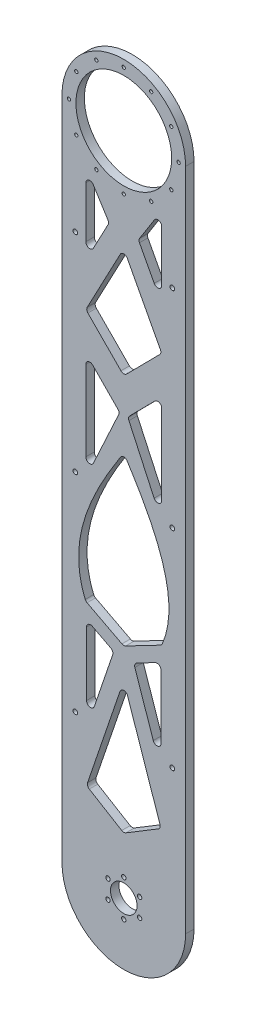
SolidWorks part; units mm, degrees
material "1060 Alloy"
ref_plane "Front Plane" through (0, 0, 0) normal (0, 0, 1) x (1, 0, 0)
ref_plane "Top Plane" through (0, 0, 0) normal (0, 1, 0) x (1, 0, 0)
ref_plane "Right Plane" through (0, 0, 0) normal (1, 0, 0) x (0, 0, -1)
sketch "Sketch2" plane through (0, 0, 0) normal (0, 0, 1) x (1, 0, 0)
  line L0 (0, 0) -> (0, 500) construction
  line L1 (-46.5, 0) -> (-46.5, 500)
  line L2 (46.5, 0) -> (46.5, 500)
  arc A0 (-46.5, 0) -> (46.5, 0) centre (0, 0) ccw
  arc A1 (46.5, 500) -> (-46.5, 500) centre (0, 500) ccw
  circle A2 centre (0, 500) radius 37.25 construction
  circle A3 centre (0, 0) radius 10
  circle A4 centre (0, 13.75) radius 1.65
  circle A5 centre (0, 0) radius 13.75 construction
  circle A6 centre (11.9078, 6.875) radius 1.65
  circle A7 centre (11.9078, -6.875) radius 1.65
  circle A8 centre (0, -13.75) radius 1.65
  circle A9 centre (-11.9078, -6.875) radius 1.65
  circle A10 centre (-11.9078, 6.875) radius 1.65
  point P3 (0, 250)
  point P27 (0, 0)
  dimension "D2" = 74.5
  dimension "D4" = 20
  dimension "D5" = 3.3
  dimension "D6" = 27.5
  dimension "D3" = 46.5
  dimension "D1" = 500
  dimension "D7" = 6
extrude "Boss-Extrude1" add sketch "Sketch2" along normal blind 6.35
sketch "Sketch4" plane through (0, 0, 6.35) normal (0, 0, 1) x (1, 0, 0)
  line L0 (0, 500) -> (0, 999.1647) construction
  line L29 (46.5, 500) -> (-46.5, 500) construction
  line L31 (28.0053, 59.376) -> (0, 42.4117)
  line L32 (0, 141.6934) -> (28.0053, 59.376)
  line L33 (-28.0053, 59.376) -> (0, 141.6934)
  line L34 (0, 42.4117) -> (-28.0053, 59.376)
  line L35 (-7.5, 156.9059) -> (-28.0053, 96.6336)
  line L36 (-28.0053, 167.5829) -> (-7.5, 156.9059)
  line L37 (-28.0053, 96.6336) -> (-28.0053, 167.5829)
  line L38 (28.0053, 167.5829) -> (7.5, 156.9059)
  line L39 (28.0053, 96.6336) -> (28.0053, 167.5829)
  line L40 (7.5, 156.9059) -> (28.0053, 96.6336)
  line L41 (0, 164.2751) -> (28.5505, 179.1412)
  line L42 (0, 164.2751) -> (-28.5505, 179.1412)
  line L43 (28.5505, 259.5868) -> (3, 314.9383)
  line L44 (28.5505, 340.7931) -> (28.5505, 259.5868)
  line L45 (3, 314.9383) -> (28.5505, 340.7931)
  line L46 (-3, 314.9383) -> (-28.5505, 340.7931)
  line L47 (-28.5505, 259.5868) -> (-3, 314.9383)
  line L48 (-28.5505, 340.7931) -> (-28.5505, 259.5868)
  line L49 (0, 423.1428) -> (-28.5505, 369.2462)
  line L50 (-28.5505, 369.2462) -> (0, 340.3557)
  line L51 (0, 340.3557) -> (28.5505, 369.2462)
  line L52 (0, 423.1428) -> (28.5505, 369.2462)
  line L53 (-28.5505, 462.0952) -> (-28.5505, 401.2902)
  line L54 (-11, 434.4215) -> (-28.5505, 462.0952)
  line L55 (-28.5505, 401.2902) -> (-11, 434.4215)
  line L56 (28.5505, 401.2902) -> (11, 434.4215)
  line L57 (28.5505, 462.0952) -> (28.5505, 401.2902)
  line L58 (11, 434.4215) -> (28.5505, 462.0952)
  arc A0 (46.5, 500) -> (-46.5, 500) centre (0, 500) ccw construction
  arc A1 (46.5, 500) -> (-46.5, 500) centre (0, 500) ccw construction
  spline S2 degree 3 poles (28.5505, 179.1412) (45.3203, 216.9857) (19.4301, 259.7903) (0, 290.0258) knots 0 0 0 0 1 1 1 1
  spline S3 degree 3 poles (-28.5505, 179.1412) (-45.3203, 216.9857) (-19.4301, 259.7903) (0, 290.0258) knots 0 0 0 0 1 1 1 1
extrude "Cut-Extrude1" cut sketch "Sketch4" against normal blind 10
fillet "Fillet3" radius 3 30 edges at (-11, 434.4215, 3.175) (-28.5505, 401.2902, 3.175) (28.5505, 401.2902, 3.175) (11, 434.4215, 3.175) (28.5505, 462.0952, 3.175) (-28.5505, 462.0952, 3.175) (0, 423.1428, 3.175) (-28.5505, 369.2462, 3.175) (28.5505, 369.2462, 3.175) (0, 340.3557, 3.175) (28.5505, 340.7931, 3.175) (-28.5505, 340.7931, 3.175) (-3, 314.9383, 3.175) (3, 314.9383, 3.175) (28.5505, 259.5868, 3.175) (-28.5505, 259.5868, 3.175) (28.5505, 179.1412, 3.175) (0, 290.0258, 3.175) (-28.5505, 179.1412, 3.175) (0, 164.2751, 3.175) (-28.0053, 96.6336, 3.175) (28.0053, 96.6336, 3.175) (7.5, 156.9059, 3.175) (-28.0053, 167.5829, 3.175) (28.0053, 167.5829, 3.175) (0, 141.6934, 3.175) (28.0053, 59.376, 3.175) (-28.0053, 59.376, 3.175) (0, 42.4117, 3.175) (-7.5, 156.9059, 3.175)
sketch "Sketch5" plane through (0, 0, 6.35) normal (0, 0, 1) x (1, 0, 0)
  line L0 (0, -46.5) -> (108.8395, -46.5) construction
  line L1 (46.5, 100) -> (-46.5, 100) construction
  line L2 (46.5, 0) -> (46.5, 500) construction
  line L3 (-46.5, 500) -> (-46.5, 0) construction
  line L4 (-46.5, 106.35) -> (46.5, 106.35) construction
  line L5 (36.5, 106.35) -> (36.5, 100) construction
  line L6 (0, 106.35) -> (0, 100) construction
  line L7 (-46.5, 256.35) -> (46.5, 256.35) construction
  line L8 (-46.5, 181.35) -> (46.5, 181.35) construction
  line L9 (-46.5, 337.7) -> (46.5, 337.7) construction
  arc A1 (-46.5, 0) -> (46.5, 0) centre (0, 0) ccw construction
  circle A2 centre (36.5, 103.175) radius 1.75
  circle A3 centre (-36.5, 103.175) radius 1.75
  circle A4 centre (36.5, 259.525) radius 1.75
  circle A5 centre (-36.5, 259.525) radius 1.75
  circle A6 centre (36.5, 415.875) radius 1.75
  circle A7 centre (-36.5, 415.875) radius 1.75
  point P18 (36.5, 103.175)
  dimension "D2" = 3.5
  dimension "D1" = 146.5
  dimension "D3" = 10
  dimension "D4" = 6.35
  dimension "D5" = 150
  dimension "D6" = 81.35
  dimension "D7" = 81.35
extrude "Cut-Extrude2" cut sketch "Sketch5" against normal through all
sketch "Sketch6" plane through (0, 0, 6.35) normal (0, 0, 1) x (1, 0, 0)
  circle A0 centre (0, 500) radius 26.5
  arc A1 (46.5, 500) -> (-46.5, 500) centre (0, 500) ccw construction
  arc A2 (46.5, 500) -> (-46.5, 500) centre (0, 500) ccw construction
  dimension "D1" = 20
extrude "Cut-Extrude3" cut sketch "Sketch6" against normal blind 10
sketch "Sketch7" plane through (0, 0, 6.35) normal (0, 0, 1) x (1, 0, 0)
  line L1 (40.0163, 523.6842) -> (44.1104, 529.9682) construction
  line L2 (23.6842, 540.0163) -> (29.9682, 544.1104) construction
  line L3 (44.1104, 529.9682) -> (29.9682, 544.1104)
  line L4 (0, 500) -> (37.0393, 537.0393) construction
  line L5 (0, 500) -> (0, 546.5) construction
  arc A0 (46.5, 500) -> (-46.5, 500) centre (0, 500) ccw construction
  arc A1 (29.9682, 544.1104) -> (16.4747, 543.4837) centre (22.4977, 559.381) cw
  arc A2 (44.1104, 529.9682) -> (43.4837, 516.4747) centre (59.381, 522.4977) ccw
  arc A3 (16.4747, 543.4837) -> (43.4837, 516.4747) centre (0, 500) cw
  dimension "D3" = 17
  dimension "D5" = 17
  dimension "D1" = 20
  dimension "D2" = 7.5
  dimension "D4" = 8
  dimension "D6" = 8
  dimension "D7" = 45
extrude "Boss-Extrude2" add sketch "Sketch7" against normal up to surface (6.35 mm away) up to face at (26.5, 500, 0)
sketch "Sketch8" plane through (287.0393, 287.0393, 0) normal (0.7071, 0.7071, 0) x (0, 0, -1)
  line L0 (0, 363.5534) -> (-6.35, 363.5534) construction
  line L1 (0, 343.5534) -> (-6.35, 343.5534) construction
  line L2 (-6.35, 343.5534) -> (-6.35, 363.5534) construction
  point P0 (-3.175, 359.5534)
  point P1 (-3.175, 347.5534)
  dimension "D1" = 4
  dimension "D2" = 4
  dimension "D3" = 3.175
hole_wizard "Tap Drill for M3x0.5 Tap1" positions "Sketch8" profile "Sketch9" hole size "M3x0.5" standard "ANSI Metric"
sketch "Sketch9" plane through (32.7967, 541.282, 3.175) normal (0, 0, 1) x (-0.7071, 0.7071, 0)
  line L0 (0, 0) -> (0, 5.7511)
  line L1 (0, 5.7511) -> (1.25, 5)
  line L2 (1.25, 5) -> (1.25, 0)
  line L5 (1.25, 0) -> (0, 0)
  line L10 (0, 5.7511) -> (-1.25, 5) construction
  line L11 (0, -6.35) -> (0, 107.95) construction
  dimension "Hole Dia." = 2.5
  dimension "Hole Depth" = 5
  dimension "Drill Angle" = 118
pattern_circular "CirPattern2" count 2 every 90 about axis through (0, 500, -3.65) along (0, 0, 1) of "Boss-Extrude2", "Tap Drill for M3x0.5 Tap1"
sketch "Sketch10" plane through (0, 0, 6.35) normal (0, 0, 1) x (1, 0, 0)
  line L0 (-43.4837, 516.4747) -> (-63.4837, 516.4747)
  line L1 (43.4837, 516.4747) -> (63.4837, 516.4747)
  arc A0 (43.4837, 516.4747) -> (-43.4837, 516.4747) centre (0, 500) ccw
  arc A1 (46.5, 500) -> (43.4837, 516.4747) centre (0, 500) ccw construction
  arc A2 (-63.4837, 516.4747) -> (63.4837, 516.4747) centre (0, 500) cw
  dimension "D1" = 19.0866
  dimension "D2" = 20
extrude "Cut-Extrude4" cut sketch "Sketch10" against normal through all
sketch "Sketch11" plane through (0, 0, 6.35) normal (0, 0, 1) x (1, 0, 0)
  circle A0 centre (0, 500) radius 36
  circle A1 centre (0, 500) radius 26.5 construction
  dimension "D1" = 72
extrude "Cut-Extrude5" cut sketch "Sketch11" against normal through all
sketch "Sketch12" plane through (0, 0, 6.35) normal (0, 0, 1) x (1, 0, 0)
  line L0 (0, 536) -> (0, 546.5) construction
  circle A0 centre (0, 500) radius 41.25 construction
  circle A1 centre (0, 500) radius 36 construction
  arc A2 (46.5, 500) -> (-46.5, 500) centre (0, 500) ccw construction
  circle A3 centre (0, 541.25) radius 1.25
  circle A4 centre (20.625, 535.7235) radius 1.25
  circle A5 centre (35.7235, 520.625) radius 1.25
  circle A6 centre (41.25, 500) radius 1.25
  circle A7 centre (35.7235, 479.375) radius 1.25
  circle A8 centre (20.625, 464.2765) radius 1.25
  circle A9 centre (0, 458.75) radius 1.25
  circle A10 centre (-20.625, 464.2765) radius 1.25
  circle A11 centre (-35.7235, 479.375) radius 1.25
  circle A12 centre (-41.25, 500) radius 1.25
  circle A13 centre (-35.7235, 520.625) radius 1.25
  circle A14 centre (-20.625, 535.7235) radius 1.25
  point P9 (0, 541.25)
  point P36 (0, 500)
  dimension "D1" = 2.5
  dimension "D2" = 12
extrude "Cut-Extrude6" cut sketch "Sketch12" against normal through all both and the other way through all
equation "\"L1L\"=500"
equation "\"L1Thick\"=6.35"
equation "\"D1@Sketch2\"=\"L1L\""
equation "\"Harm-Drive-Outer\"=74.5"
equation "\"D2@Sketch2\"=\"Harm-Drive-Outer\""
equation "\"D1@Boss-Extrude1\"=\"L1Thick\""
